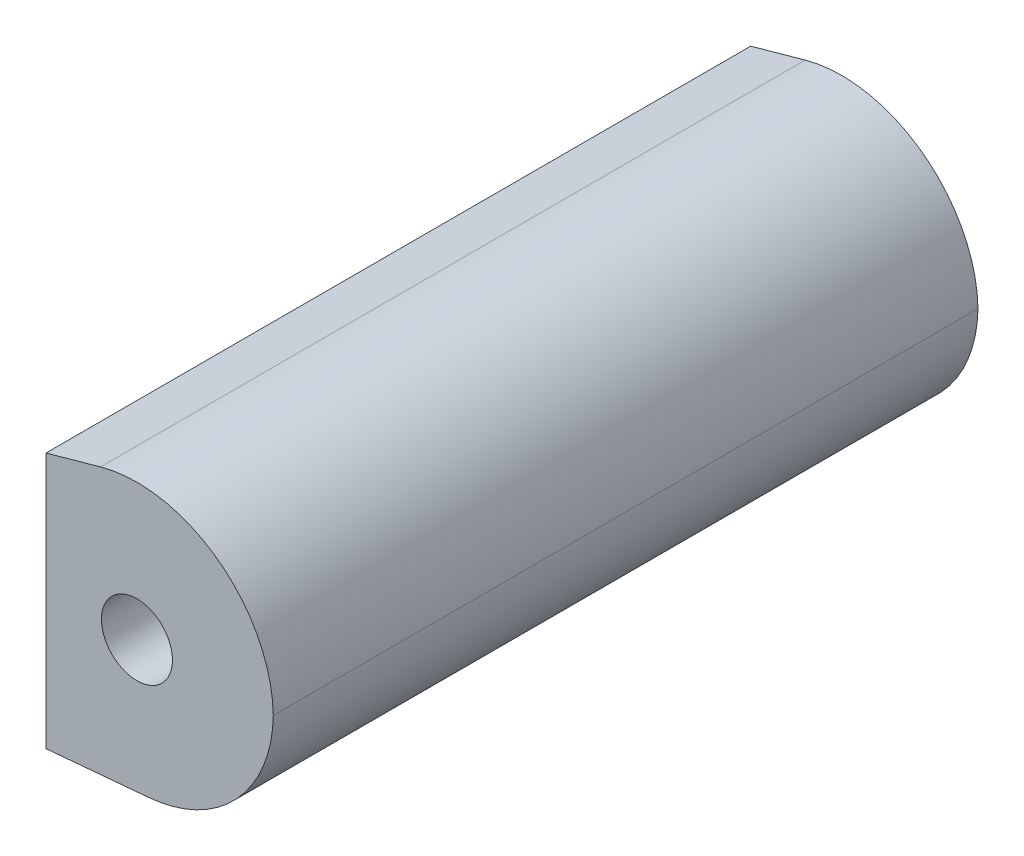
SolidWorks part; units mm, degrees
ref_plane "Front Plane" through (0, 0, 0) normal (0, 0, 1) x (1, 0, 0)
ref_plane "Top Plane" through (0, 0, 0) normal (0, 1, 0) x (1, 0, 0)
ref_plane "Right Plane" through (0, 0, 0) normal (1, 0, 0) x (0, 0, -1)
sketch "Sketch1" plane through (0, 0, 0) normal (0, 0, 1) x (1, 0, 0)
  circle A2 centre (19.9332, 5.0443) radius 1.9844
  arc A3 (20.568, -2.2627) -> (27.5519, 5.1875) centre (19.9332, 5.3308) ccw
  arc A4 (27.5519, 5.1875) -> (17.8991, 12.3878) centre (19.9332, 5.0443) ccw
  spline S0 degree 3 poles (-43.5668, -9.1185) (-37.6773, -7.6477) (-27.7099, -7.0247) (-9.9845, -4.6043) (5.4332, -3.6912) (16.9241, -2.5678) (20.5343, -2.2656) (20.568, -2.2627) knots 0.794337 0.794337 0.794337 0.794337 0.852124 0.889612 0.965358 0.999676 1 1 1 1
  spline S1 degree 3 poles (17.8991, 12.3878) (11.779, 10.6925) (-2.9586, 6.4319) (-24.0803, -0.4076) (-34.9936, -4.7358) (-48.5374, -9.6348) (-43.5668, -9.1185) knots 0 0 0 0 0.056261 0.133579 0.179881 0.203823 0.203823 0.203823 0.203823
  dimension "D2" = 3.9688
  dimension "D1" = 64.1348
extrude "Boss-Extrude1" add sketch "Sketch1" along normal blind 39.37
sketch "Sketch3" plane through (0, 0, 39.37) normal (0, 0, 1) x (1, 0, 0)
  line L1 (-50.0795, 23.2318) -> (14.8519, 23.2318)
  line L2 (-50.0795, 23.2318) -> (-50.0795, -18.0197)
  line L3 (-50.0795, -18.0197) -> (14.8519, -18.0197)
  line L4 (14.8519, 23.2318) -> (14.8519, -18.0197)
  dimension "D1" = 12.7
extrude "Cut-Extrude2" cut sketch "Sketch3" against normal through all both
